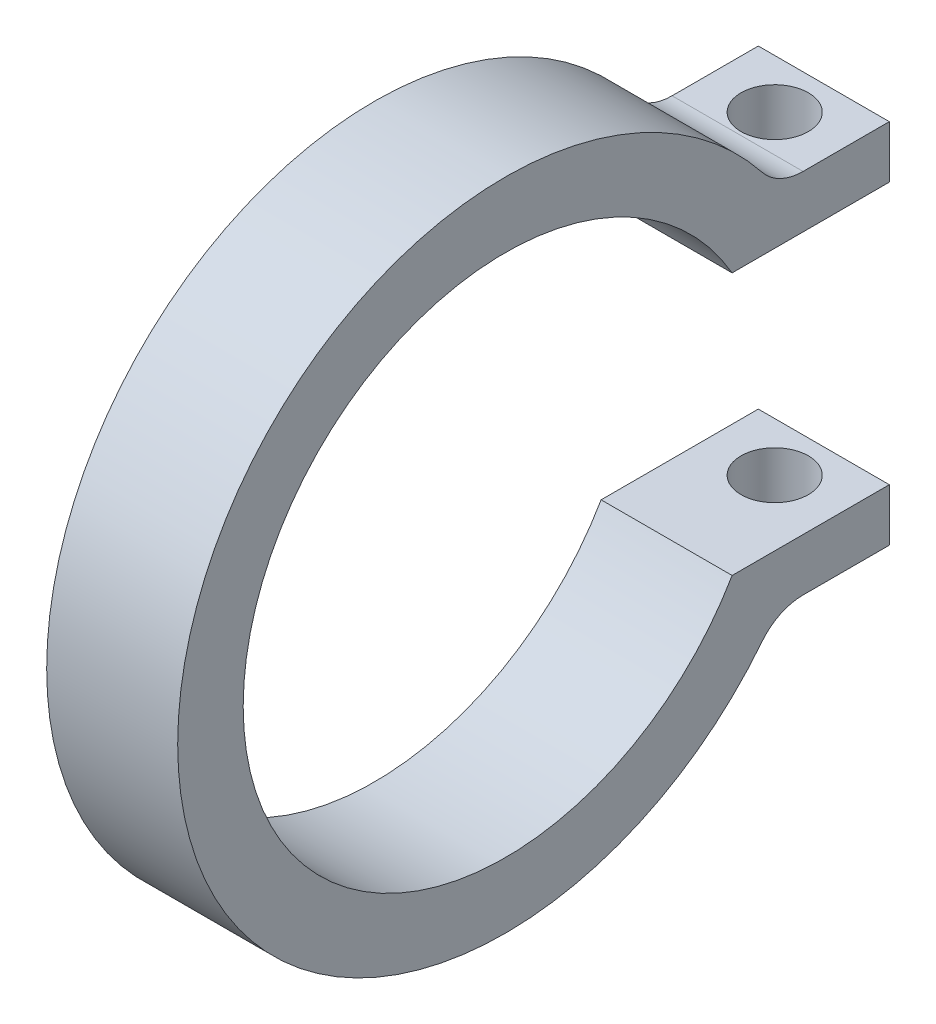
SolidWorks part; units mm, degrees
material "6061-T6 (SS)"
ref_plane "Front Plane" through (0, 0, 0) normal (1, 0, 0) x (0, 1, 0)
ref_plane "Top Plane" through (0, 0, 0) normal (0, 0, 1) x (0, 1, 0)
ref_plane "Right Plane" through (0, 0, 0) normal (0, 1, 0) x (-1, 0, 0)
sketch "Sketch2" plane through (0, 0, 0) normal (1, 0, 0) x (0, 1, 0)
  line L0 (-6.35, -10.9985) -> (6.35, -10.9985) construction
  line L1 (-6.35, -10.9985) -> (-6.35, -18.6185)
  line L2 (6.35, -10.9985) -> (6.35, -18.6185)
  line L3 (-8.89, -13.1523) -> (-8.89, -18.6185)
  line L4 (-8.89, -18.6185) -> (-6.35, -18.6185)
  line L5 (6.35, -18.6185) -> (8.89, -18.6185)
  line L6 (8.89, -18.6185) -> (8.89, -13.1523)
  line L7 (-3.175, -12.2967) -> (3.175, -12.2967) construction
  arc A0 (6.35, -10.9985) -> (-6.35, -10.9985) centre (0, 0) ccw
  arc A1 (8.89, -13.1523) -> (-8.89, -13.1523) centre (0, 0) ccw
  circle A2 centre (0, 0) radius 12.7 construction
  point P13 (-2.7389, -12.4012)
  point P14 (3.1198, -12.3108)
  dimension "D2" = 12.7
  dimension "D4" = 15.875
  dimension "D1" = 12.7
  dimension "D3" = 7.62
  dimension "D5" = 2.54
  dimension "D6" = 2.54
  dimension "D7" = 6.35
  dimension "D8" = 6.3218
extrude "Boss-Extrude1" add sketch "Sketch2" along normal blind 6.35
sketch "Sketch3" plane through (0, -8.89, 0) normal (0, -1, 0) x (1, 0, 0)
  line L1 (3.175, -13.1523) -> (3.175, -18.6185) construction
  line L2 (6.35, -13.1523) -> (0, -13.1523) construction
  line L3 (6.35, -18.6185) -> (0, -18.6185) construction
  point P9 (3.175, -16.2373)
  dimension "D1" = 2.3813
hole_wizard "#4 Clearance Hole1" positions "Sketch3" profile "Sketch4" hole size "#4" standard "ANSI Inch" end condition through all
sketch "Sketch4" plane through (3.175, -8.89, -16.2373) normal (1, 0, 0) x (0, 0, -1)
  line L0 (0, 0) -> (0, 24.765)
  line L1 (0, 24.765) -> (1.6319, 24.765)
  line L2 (1.6319, 24.765) -> (1.6319, 0)
  line L5 (1.6319, 0) -> (0, 0)
  line L11 (0, -6.35) -> (0, 107.95) construction
  dimension "Thru Hole Dia." = 3.2639
  dimension "Thru Hole Depth" = 24.765
fillet "Fillet2" radius 2.54 2 edges at (3.175, 8.89, -13.1523) (3.175, -8.89, -13.1523)
